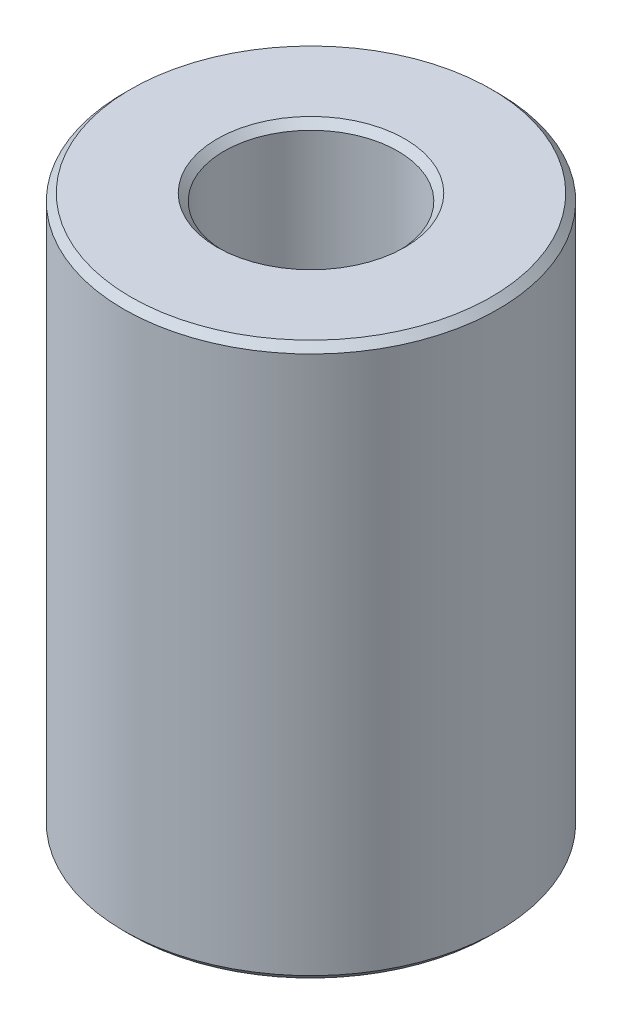
SolidWorks part; units mm, degrees
ref_plane "Front Plane" through (0, 0, 0) normal (0, 0, 1) x (1, 0, 0)
ref_plane "Top Plane" through (0, 0, 0) normal (0, 1, 0) x (1, 0, 0)
ref_plane "Right Plane" through (0, 0, 0) normal (1, 0, 0) x (0, 0, -1)
sketch "Sketch1" plane through (0, 0, 0) normal (0, 1, 0) x (1, 0, 0)
  circle A0 centre (0, 0) radius 47.5
  dimension "SLEEVE_OD" = 95
extrude "Boss-Extrude1" add sketch "Sketch1" along normal blind 140.1904
sketch "Sketch2" plane through (0, 0, 0) normal (0, 1, 0) x (1, 0, 0)
  circle A0 centre (0, 0) radius 22.0452
  dimension "BORE_D" = 44.0904
extrude "Cut-Extrude1" cut sketch "Sketch2" along normal through all
chamfer "Chamfer1" distance 1.7852 angle 45 4 edges at (0, 140.1904, 22.0452) (0, 0, 22.0452) (0, 0, 47.5) (0, 140.1904, 47.5)
